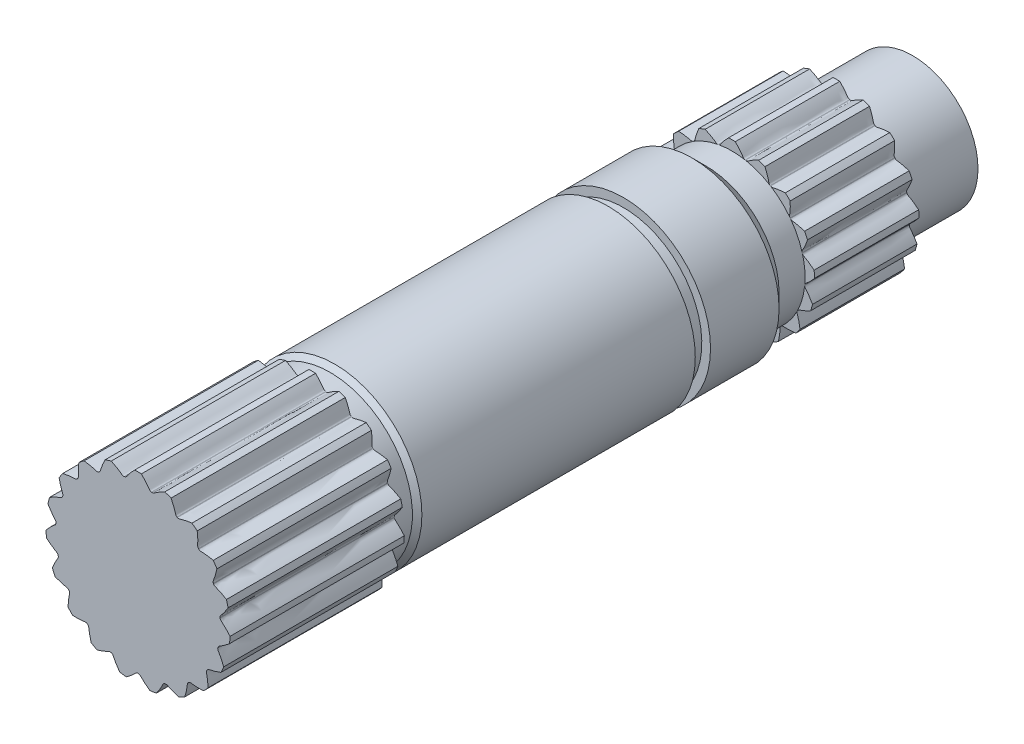
SolidWorks part; units mm, degrees
material "Alloy Steel"
ref_plane "Front Plane" through (0, 0, 0) normal (0, 0, 1) x (1, 0, 0)
ref_plane "Top Plane" through (0, 0, 0) normal (0, 1, 0) x (1, 0, 0)
ref_plane "Right Plane" through (0, 0, 0) normal (1, 0, 0) x (0, 0, -1)
sketch "Sketch12" plane through (0, 0, 0) normal (0, 0, 1) x (1, 0, 0)
  circle A0 centre (0, 0) radius 10
  dimension "D1" = 20
extrude "Shaft" add sketch "Sketch12" along normal mid plane 45
sketch "Sketch13" plane through (0, 0, 22.5) normal (0, 0, 1) x (1, 0, 0)
  circle A0 centre (0, 0) radius 9.4556
  dimension "D1" = 18.9113
extrude "Motor side relief" add sketch "Sketch13" along normal blind 1.587
sketch "Sketch14" plane through (0, 0, -22.5) normal (0, 0, -1) x (-1, 0, 0)
  circle A0 centre (0, 0) radius 8.3981
  dimension "D1" = 16.7963
extrude "Gear side relief" add sketch "Sketch14" along normal blind 1.587
sketch "Sketch15" plane through (0, 0, 24.087) normal (0, 0, 1) x (1, 0, 0)
  line L0 (5.7898, -7.4758) -> (5.8078, -7.4618)
  line L1 (5.8078, -7.4618) -> (5.8257, -7.4478)
  line L2 (7.9035, -5.1908) -> (7.9159, -5.1717)
  line L3 (7.9159, -5.1717) -> (7.9284, -5.1527)
  line L4 (9.1607, -2.3432) -> (9.1663, -2.3212)
  line L5 (9.1663, -2.3212) -> (9.1719, -2.2992)
  line L6 (9.4252, 0.7582) -> (9.4233, 0.7808)
  line L7 (9.4233, 0.7808) -> (9.4214, 0.8035)
  line L8 (8.6683, 3.7775) -> (8.6592, 3.7983)
  line L9 (8.6592, 3.7983) -> (8.6501, 3.8191)
  line L10 (6.9721, 6.3874) -> (6.9567, 6.4041)
  line L11 (6.9567, 6.4041) -> (6.9413, 6.4208)
  line L12 (4.5204, 8.3051) -> (4.5004, 8.316)
  line L13 (4.5004, 8.316) -> (4.4804, 8.3268)
  line L14 (1.5788, 9.3229) -> (1.5563, 9.3267)
  line L15 (1.5563, 9.3267) -> (1.5339, 9.3304)
  line L16 (-1.5339, 9.3304) -> (-1.5563, 9.3267)
  line L17 (-1.5563, 9.3267) -> (-1.5788, 9.3229)
  line L18 (-4.4804, 8.3268) -> (-4.5004, 8.316)
  line L19 (-4.5004, 8.316) -> (-4.5204, 8.3051)
  line L20 (-6.9413, 6.4208) -> (-6.9567, 6.4041)
  line L21 (-6.9567, 6.4041) -> (-6.9721, 6.3874)
  line L22 (-8.6501, 3.8191) -> (-8.6592, 3.7983)
  line L23 (-8.6592, 3.7983) -> (-8.6683, 3.7775)
  line L24 (-9.4214, 0.8035) -> (-9.4233, 0.7808)
  line L25 (-9.4233, 0.7808) -> (-9.4252, 0.7582)
  line L26 (-9.1719, -2.2992) -> (-9.1663, -2.3212)
  line L27 (-9.1663, -2.3212) -> (-9.1607, -2.3432)
  line L28 (-7.9284, -5.1527) -> (-7.9159, -5.1717)
  line L29 (-7.9159, -5.1717) -> (-7.9035, -5.1908)
  line L30 (-5.8257, -7.4478) -> (-5.8078, -7.4618)
  line L31 (-5.8078, -7.4618) -> (-5.7898, -7.4758)
  line L32 (-3.0917, -8.9359) -> (-3.0702, -8.9433)
  line L33 (-3.0702, -8.9433) -> (-3.0487, -8.9507)
  line L34 (-0.0227, -9.4556) -> (0, -9.4556)
  line L35 (0, -9.4556) -> (0.0227, -9.4556)
  line L36 (3.0487, -8.9507) -> (3.0702, -8.9433)
  line L37 (3.0702, -8.9433) -> (3.0917, -8.9359)
  arc A0 (4.6925, -9.4774) -> (5.3676, -9.1121) centre (0, 0) ccw
  arc A1 (7.5156, -7.4402) -> (8.0355, -6.8755) centre (0, 0) ccw
  arc A2 (9.5242, -4.5968) -> (9.8326, -3.8939) centre (0, 0) ccw
  arc A3 (10.5007, -1.2552) -> (10.5641, -0.4903) centre (0, 0) ccw
  arc A4 (10.3394, 2.2224) -> (10.1509, 2.9665) centre (0, 0) ccw
  arc A5 (9.0575, 5.4591) -> (8.6377, 6.1017) centre (0, 0) ccw
  arc A6 (6.7942, 8.1043) -> (6.1885, 8.5758) centre (0, 0) ccw
  arc A7 (3.7946, 9.8713) -> (3.0686, 10.1205) centre (0, 0) ccw
  arc A8 (0.3838, 10.5685) -> (-0.3838, 10.5685) centre (0, 0) ccw
  arc A9 (-3.0686, 10.1205) -> (-3.7946, 9.8713) centre (0, 0) ccw
  arc A10 (-6.1885, 8.5758) -> (-6.7942, 8.1043) centre (0, 0) ccw
  arc A11 (-8.6377, 6.1017) -> (-9.0575, 5.4591) centre (0, 0) ccw
  arc A12 (-10.1509, 2.9665) -> (-10.3394, 2.2224) centre (0, 0) ccw
  arc A13 (-10.5641, -0.4903) -> (-10.5007, -1.2552) centre (0, 0) ccw
  arc A14 (-9.8326, -3.8939) -> (-9.5242, -4.5968) centre (0, 0) ccw
  arc A15 (-8.0355, -6.8755) -> (-7.5156, -7.4402) centre (0, 0) ccw
  arc A16 (-5.3676, -9.1121) -> (-4.6925, -9.4774) centre (0, 0) ccw
  arc A17 (-2.1181, -10.3612) -> (-1.361, -10.4876) centre (0, 0) ccw
  arc A18 (1.361, -10.4876) -> (2.1181, -10.3612) centre (0, 0) ccw
  spline S0 degree 3 poles (3.0917, -8.9359) (3.1544, -8.9142) (3.2184, -8.911) (3.3396, -8.938) (3.397, -8.9729) (3.5767, -9.0624) (3.828, -9.1783) (4.24, -9.3384) (4.5379, -9.4334) (4.6925, -9.4774) knots 0 0 0 0 0.125 0.125 0.25 0.25 0.5 0.75 1 1 1 1
  spline S1 degree 3 poles (5.3676, -9.1121) (5.4153, -8.9586) (5.4987, -8.6572) (5.5901, -8.2247) (5.6305, -7.951) (5.6538, -7.7516) (5.656, -7.6845) (5.6997, -7.5682) (5.7374, -7.5164) (5.7898, -7.4758) knots 0 0 0 0 0.25 0.5 0.75 0.75 0.875 0.875 1 1 1 1
  spline S2 degree 3 poles (5.8257, -7.4478) (5.8779, -7.407) (5.9374, -7.3832) (6.0608, -7.3694) (6.1265, -7.3837) (6.3255, -7.41) (6.6008, -7.438) (7.0425, -7.4557) (7.3551, -7.4488) (7.5156, -7.4402) knots 0 0 0 0 0.125 0.125 0.25 0.25 0.5 0.75 1 1 1 1
  spline S3 degree 3 poles (8.0355, -6.8755) (8.0308, -6.7148) (8.0117, -6.4027) (7.9577, -5.964) (7.9071, -5.692) (7.8645, -5.4958) (7.8447, -5.4316) (7.8483, -5.3075) (7.8671, -5.2462) (7.9035, -5.1908) knots 0 0 0 0 0.25 0.5 0.75 0.75 0.875 0.875 1 1 1 1
  spline S4 degree 3 poles (7.9284, -5.1527) (7.9645, -5.0971) (8.013, -5.0552) (8.1253, -5.0021) (8.192, -4.9944) (8.3888, -4.9546) (8.6583, -4.8918) (9.0817, -4.765) (9.3752, -4.6571) (9.5242, -4.5968) knots 0 0 0 0 0.125 0.125 0.25 0.25 0.5 0.75 1 1 1 1
  spline S5 degree 3 poles (9.8326, -3.8939) (9.7759, -3.7434) (9.6566, -3.4544) (9.4631, -3.057) (9.3268, -2.8161) (9.2228, -2.6445) (9.1833, -2.5901) (9.1463, -2.4716) (9.1443, -2.4075) (9.1607, -2.3432) knots 0 0 0 0 0.25 0.5 0.75 0.75 0.875 0.875 1 1 1 1
  spline S6 degree 3 poles (9.1719, -2.2992) (9.188, -2.2349) (9.2203, -2.1795) (9.3092, -2.0928) (9.3699, -2.0638) (9.543, -1.9624) (9.7775, -1.8154) (10.1368, -1.558) (10.3793, -1.3606) (10.5007, -1.2552) knots 0 0 0 0 0.125 0.125 0.25 0.25 0.5 0.75 1 1 1 1
  spline S7 degree 3 poles (10.5641, -0.4903) (10.4617, -0.3663) (10.255, -0.1317) (9.9429, 0.1813) (9.7359, 0.3649) (9.5818, 0.4935) (9.5267, 0.532) (9.4533, 0.6322) (9.4305, 0.6921) (9.4252, 0.7582) knots 0 0 0 0 0.25 0.5 0.75 0.75 0.875 0.875 1 1 1 1
  spline S8 degree 3 poles (9.4214, 0.8035) (9.4158, 0.8695) (9.4284, 0.9324) (9.4844, 1.0433) (9.5323, 1.0904) (9.6631, 1.2426) (9.8372, 1.4577) (10.0935, 1.8179) (10.2588, 2.0833) (10.3394, 2.2224) knots 0 0 0 0 0.125 0.125 0.25 0.25 0.5 0.75 1 1 1 1
  spline S9 degree 3 poles (10.1509, 2.9665) (10.0138, 3.0504) (9.7422, 3.2052) (9.3453, 3.4) (9.0899, 3.5063) (8.9024, 3.5779) (8.8378, 3.5965) (8.7358, 3.6674) (8.6948, 3.7167) (8.6683, 3.7775) knots 0 0 0 0 0.25 0.5 0.75 0.75 0.875 0.875 1 1 1 1
  spline S10 degree 3 poles (8.6501, 3.8191) (8.6233, 3.8797) (8.6148, 3.9433) (8.6317, 4.0663) (8.6618, 4.1264) (8.7361, 4.3129) (8.8308, 4.5729) (8.9563, 4.9967) (9.0265, 5.3014) (9.0575, 5.4591) knots 0 0 0 0 0.125 0.125 0.25 0.25 0.5 0.75 1 1 1 1
  spline S11 degree 3 poles (8.6377, 6.1017) (8.4808, 6.1366) (8.1736, 6.1948) (7.735, 6.2502) (7.4588, 6.2678) (7.2583, 6.2747) (7.1911, 6.2713) (7.0717, 6.3052) (7.0169, 6.3385) (6.9721, 6.3874) knots 0 0 0 0 0.25 0.5 0.75 0.75 0.875 0.875 1 1 1 1
  spline S12 degree 3 poles (6.9413, 6.4208) (6.8963, 6.4695) (6.8676, 6.5268) (6.8437, 6.6487) (6.8526, 6.7153) (6.8624, 6.9158) (6.8676, 7.1925) (6.8486, 7.6341) (6.816, 7.9451) (6.7942, 8.1043) knots 0 0 0 0 0.125 0.125 0.25 0.25 0.5 0.75 1 1 1 1
  spline S13 degree 3 poles (6.1885, 8.5758) (6.0287, 8.5578) (5.7193, 8.5131) (5.2865, 8.4231) (5.0196, 8.3501) (4.8276, 8.2914) (4.7652, 8.2664) (4.6412, 8.2597) (4.5786, 8.2734) (4.5204, 8.3051) knots 0 0 0 0 0.25 0.5 0.75 0.75 0.875 0.875 1 1 1 1
  spline S14 degree 3 poles (4.4804, 8.3268) (4.422, 8.3582) (4.3763, 8.4031) (4.3141, 8.5106) (4.3009, 8.5765) (4.245, 8.7693) (4.1601, 9.0326) (3.9988, 9.4442) (3.8669, 9.7277) (3.7946, 9.8713) knots 0 0 0 0 0.125 0.125 0.25 0.25 0.5 0.75 1 1 1 1
  spline S15 degree 3 poles (3.0686, 10.1205) (2.9233, 10.0517) (2.6452, 9.9089) (2.2651, 9.6832) (2.0363, 9.5275) (1.8738, 9.4097) (1.8229, 9.3658) (1.7078, 9.3192) (1.6441, 9.3118) (1.5788, 9.3229) knots 0 0 0 0 0.25 0.5 0.75 0.75 0.875 0.875 1 1 1 1
  spline S16 degree 3 poles (1.5339, 9.3304) (1.4685, 9.3411) (1.4107, 9.3688) (1.3169, 9.4502) (1.283, 9.5083) (1.1676, 9.6725) (1.0018, 9.894) (0.7156, 10.2309) (0.4988, 10.4563) (0.3838, 10.5685) knots 0 0 0 0 0.125 0.125 0.25 0.25 0.5 0.75 1 1 1 1
  spline S17 degree 3 poles (-0.3838, 10.5685) (-0.4988, 10.4563) (-0.7156, 10.2309) (-1.0018, 9.894) (-1.1676, 9.6725) (-1.283, 9.5083) (-1.3169, 9.4502) (-1.4107, 9.3688) (-1.4685, 9.3411) (-1.5339, 9.3304) knots 0 0 0 0 0.25 0.5 0.75 0.75 0.875 0.875 1 1 1 1
  spline S18 degree 3 poles (-1.5788, 9.3229) (-1.6441, 9.3118) (-1.7078, 9.3192) (-1.8229, 9.3658) (-1.8738, 9.4097) (-2.0363, 9.5275) (-2.2651, 9.6832) (-2.6452, 9.9089) (-2.9233, 10.0517) (-3.0686, 10.1205) knots 0 0 0 0 0.125 0.125 0.25 0.25 0.5 0.75 1 1 1 1
  spline S19 degree 3 poles (-3.7946, 9.8713) (-3.8669, 9.7277) (-3.9988, 9.4442) (-4.1601, 9.0326) (-4.245, 8.7693) (-4.3009, 8.5765) (-4.3141, 8.5106) (-4.3763, 8.4031) (-4.422, 8.3582) (-4.4804, 8.3268) knots 0 0 0 0 0.25 0.5 0.75 0.75 0.875 0.875 1 1 1 1
  spline S20 degree 3 poles (-4.5204, 8.3051) (-4.5786, 8.2734) (-4.6412, 8.2597) (-4.7652, 8.2664) (-4.8276, 8.2914) (-5.0196, 8.3501) (-5.2865, 8.4231) (-5.7193, 8.5131) (-6.0287, 8.5578) (-6.1885, 8.5758) knots 0 0 0 0 0.125 0.125 0.25 0.25 0.5 0.75 1 1 1 1
  spline S21 degree 3 poles (-6.7942, 8.1043) (-6.816, 7.9451) (-6.8486, 7.6341) (-6.8676, 7.1925) (-6.8624, 6.9158) (-6.8526, 6.7153) (-6.8437, 6.6487) (-6.8676, 6.5268) (-6.8963, 6.4695) (-6.9413, 6.4208) knots 0 0 0 0 0.25 0.5 0.75 0.75 0.875 0.875 1 1 1 1
  spline S22 degree 3 poles (-6.9721, 6.3874) (-7.0169, 6.3385) (-7.0717, 6.3052) (-7.1911, 6.2713) (-7.2583, 6.2747) (-7.4588, 6.2678) (-7.735, 6.2502) (-8.1736, 6.1948) (-8.4808, 6.1366) (-8.6377, 6.1017) knots 0 0 0 0 0.125 0.125 0.25 0.25 0.5 0.75 1 1 1 1
  spline S23 degree 3 poles (-9.0575, 5.4591) (-9.0265, 5.3014) (-8.9563, 4.9967) (-8.8308, 4.5729) (-8.7361, 4.3129) (-8.6618, 4.1264) (-8.6317, 4.0663) (-8.6148, 3.9433) (-8.6233, 3.8797) (-8.6501, 3.8191) knots 0 0 0 0 0.25 0.5 0.75 0.75 0.875 0.875 1 1 1 1
  spline S24 degree 3 poles (-8.6683, 3.7775) (-8.6948, 3.7167) (-8.7358, 3.6674) (-8.8378, 3.5965) (-8.9024, 3.5779) (-9.0899, 3.5063) (-9.3453, 3.4) (-9.7422, 3.2052) (-10.0138, 3.0504) (-10.1509, 2.9665) knots 0 0 0 0 0.125 0.125 0.25 0.25 0.5 0.75 1 1 1 1
  spline S25 degree 3 poles (-10.3394, 2.2224) (-10.2588, 2.0833) (-10.0935, 1.8179) (-9.8372, 1.4577) (-9.6631, 1.2426) (-9.5323, 1.0904) (-9.4844, 1.0433) (-9.4284, 0.9324) (-9.4158, 0.8695) (-9.4214, 0.8035) knots 0 0 0 0 0.25 0.5 0.75 0.75 0.875 0.875 1 1 1 1
  spline S26 degree 3 poles (-9.4252, 0.7582) (-9.4305, 0.6921) (-9.4533, 0.6322) (-9.5267, 0.532) (-9.5818, 0.4935) (-9.7359, 0.3649) (-9.9429, 0.1813) (-10.255, -0.1317) (-10.4617, -0.3663) (-10.5641, -0.4903) knots 0 0 0 0 0.125 0.125 0.25 0.25 0.5 0.75 1 1 1 1
  spline S27 degree 3 poles (-10.5007, -1.2552) (-10.3793, -1.3606) (-10.1368, -1.558) (-9.7775, -1.8154) (-9.543, -1.9624) (-9.3699, -2.0638) (-9.3092, -2.0928) (-9.2203, -2.1795) (-9.188, -2.2349) (-9.1719, -2.2992) knots 0 0 0 0 0.25 0.5 0.75 0.75 0.875 0.875 1 1 1 1
  spline S28 degree 3 poles (-9.1607, -2.3432) (-9.1443, -2.4075) (-9.1463, -2.4716) (-9.1833, -2.5901) (-9.2228, -2.6445) (-9.3268, -2.8161) (-9.4631, -3.057) (-9.6566, -3.4544) (-9.7759, -3.7434) (-9.8326, -3.8939) knots 0 0 0 0 0.125 0.125 0.25 0.25 0.5 0.75 1 1 1 1
  spline S29 degree 3 poles (-9.5242, -4.5968) (-9.3752, -4.6571) (-9.0817, -4.765) (-8.6583, -4.8918) (-8.3888, -4.9546) (-8.192, -4.9944) (-8.1253, -5.0021) (-8.013, -5.0552) (-7.9645, -5.0971) (-7.9284, -5.1527) knots 0 0 0 0 0.25 0.5 0.75 0.75 0.875 0.875 1 1 1 1
  spline S30 degree 3 poles (-7.9035, -5.1908) (-7.8671, -5.2462) (-7.8483, -5.3075) (-7.8447, -5.4316) (-7.8645, -5.4958) (-7.9071, -5.692) (-7.9577, -5.964) (-8.0117, -6.4027) (-8.0308, -6.7148) (-8.0355, -6.8755) knots 0 0 0 0 0.125 0.125 0.25 0.25 0.5 0.75 1 1 1 1
  spline S31 degree 3 poles (-7.5156, -7.4402) (-7.3551, -7.4488) (-7.0425, -7.4557) (-6.6008, -7.438) (-6.3255, -7.41) (-6.1265, -7.3837) (-6.0608, -7.3694) (-5.9374, -7.3832) (-5.8779, -7.407) (-5.8257, -7.4478) knots 0 0 0 0 0.25 0.5 0.75 0.75 0.875 0.875 1 1 1 1
  spline S32 degree 3 poles (-5.7898, -7.4758) (-5.7374, -7.5164) (-5.6997, -7.5682) (-5.656, -7.6845) (-5.6538, -7.7516) (-5.6305, -7.951) (-5.5901, -8.2247) (-5.4987, -8.6572) (-5.4153, -8.9586) (-5.3676, -9.1121) knots 0 0 0 0 0.125 0.125 0.25 0.25 0.5 0.75 1 1 1 1
  spline S33 degree 3 poles (-4.6925, -9.4774) (-4.5379, -9.4334) (-4.24, -9.3384) (-3.828, -9.1783) (-3.5767, -9.0624) (-3.397, -8.9729) (-3.3396, -8.938) (-3.2184, -8.911) (-3.1544, -8.9142) (-3.0917, -8.9359) knots 0 0 0 0 0.25 0.5 0.75 0.75 0.875 0.875 1 1 1 1
  spline S34 degree 3 poles (-3.0487, -8.9507) (-2.986, -8.972) (-2.9335, -9.0088) (-2.8544, -9.1046) (-2.8306, -9.1674) (-2.7437, -9.3484) (-2.6166, -9.5942) (-2.3898, -9.9736) (-2.2131, -10.2315) (-2.1181, -10.3612) knots 0 0 0 0 0.125 0.125 0.25 0.25 0.5 0.75 1 1 1 1
  spline S35 degree 3 poles (-1.361, -10.4876) (-1.229, -10.3957) (-0.9781, -10.2091) (-0.6404, -9.9239) (-0.4404, -9.7327) (-0.2995, -9.5898) (-0.2565, -9.5381) (-0.1506, -9.4732) (-0.089, -9.4555) (-0.0227, -9.4556) knots 0 0 0 0 0.25 0.5 0.75 0.75 0.875 0.875 1 1 1 1
  spline S36 degree 3 poles (0.0227, -9.4556) (0.089, -9.4555) (0.1506, -9.4732) (0.2565, -9.5381) (0.2995, -9.5898) (0.4404, -9.7327) (0.6404, -9.9239) (0.9781, -10.2091) (1.229, -10.3957) (1.361, -10.4876) knots 0 0 0 0 0.125 0.125 0.25 0.25 0.5 0.75 1 1 1 1
  spline S37 degree 3 poles (2.1181, -10.3612) (2.2131, -10.2315) (2.3898, -9.9736) (2.6166, -9.5942) (2.7437, -9.3484) (2.8306, -9.1674) (2.8544, -9.1046) (2.9335, -9.0088) (2.986, -8.972) (3.0487, -8.9507) knots 0 0 0 0 0.25 0.5 0.75 0.75 0.875 0.875 1 1 1 1
extrude "Boss-Extrude8" add sketch "Sketch15" along normal blind 20
sketch "Sketch17" plane through (0, 0, -24.087) normal (0, 0, -1) x (-1, 0, 0)
  line L38 (4.4402, 7.1283) -> (4.4211, 7.1402)
  line L39 (4.4211, 7.1402) -> (4.4019, 7.1521)
  line L40 (1.5653, 8.251) -> (1.5432, 8.2552)
  line L41 (1.5432, 8.2552) -> (1.521, 8.2593)
  line L42 (-1.521, 8.2593) -> (-1.5432, 8.2552)
  line L43 (-1.5432, 8.2552) -> (-1.5653, 8.251)
  line L44 (-4.4019, 7.1521) -> (-4.4211, 7.1402)
  line L45 (-4.4211, 7.1402) -> (-4.4402, 7.1283)
  line L46 (-6.6882, 5.079) -> (-6.7019, 5.061)
  line L47 (-6.7019, 5.061) -> (-6.7154, 5.043)
  line L48 (-8.0713, 2.32) -> (-8.0776, 2.2983)
  line L49 (-8.0776, 2.2983) -> (-8.0837, 2.2766)
  line L50 (-8.3644, -0.7524) -> (-8.3623, -0.7749)
  line L51 (-8.3623, -0.7749) -> (-8.3602, -0.7973)
  line L52 (-7.5277, -3.7232) -> (-7.5177, -3.7434)
  line L53 (-7.5177, -3.7434) -> (-7.5076, -3.7636)
  line L54 (-5.6744, -6.1911) -> (-5.6578, -6.2063)
  line L55 (-5.6578, -6.2063) -> (-5.6411, -6.2215)
  line L56 (-3.0548, -7.8229) -> (-3.0338, -7.831)
  line L57 (-3.0338, -7.831) -> (-3.0127, -7.8392)
  line L58 (-0.0226, -8.3981) -> (0, -8.3981)
  line L59 (0, -8.3981) -> (0.0226, -8.3981)
  line L60 (3.0127, -7.8392) -> (3.0338, -7.831)
  line L61 (3.0338, -7.831) -> (3.0548, -7.8229)
  line L62 (5.6411, -6.2215) -> (5.6578, -6.2063)
  line L63 (5.6578, -6.2063) -> (5.6744, -6.1911)
  line L64 (7.5076, -3.7636) -> (7.5177, -3.7434)
  line L65 (7.5177, -3.7434) -> (7.5277, -3.7232)
  line L66 (8.3602, -0.7973) -> (8.3623, -0.7749)
  line L67 (8.3623, -0.7749) -> (8.3644, -0.7524)
  line L68 (8.0837, 2.2766) -> (8.0776, 2.2983)
  line L69 (8.0776, 2.2983) -> (8.0713, 2.32)
  line L70 (6.7154, 5.043) -> (6.7019, 5.061)
  line L71 (6.7019, 5.061) -> (6.6882, 5.079)
  arc A19 (6.6912, 6.7683) -> (6.1221, 7.2872) centre (0, 0) ccw
  arc A20 (3.7944, 8.7284) -> (3.0762, 9.0066) centre (0, 0) ccw
  arc A21 (0.3851, 9.5097) -> (-0.3851, 9.5097) centre (0, 0) ccw
  arc A22 (-3.0762, 9.0066) -> (-3.7944, 8.7284) centre (0, 0) ccw
  arc A23 (-6.1221, 7.2872) -> (-6.6912, 6.7683) centre (0, 0) ccw
  arc A24 (-8.3411, 4.5835) -> (-8.6844, 3.8941) centre (0, 0) ccw
  arc A25 (-9.4336, 1.2609) -> (-9.5047, 0.494) centre (0, 0) ccw
  arc A26 (-9.2521, -2.2321) -> (-9.0413, -2.9728) centre (0, 0) ccw
  arc A27 (-7.821, -5.4236) -> (-7.3569, -6.0382) centre (0, 0) ccw
  arc A28 (-5.3336, -7.8826) -> (-4.6788, -8.288) centre (0, 0) ccw
  arc A29 (-2.1259, -9.277) -> (-1.3689, -9.4185) centre (0, 0) ccw
  arc A30 (1.3689, -9.4185) -> (2.1259, -9.277) centre (0, 0) ccw
  arc A31 (4.6788, -8.288) -> (5.3336, -7.8826) centre (0, 0) ccw
  arc A32 (7.3569, -6.0382) -> (7.821, -5.4236) centre (0, 0) ccw
  arc A33 (9.0413, -2.9728) -> (9.2521, -2.2321) centre (0, 0) ccw
  arc A34 (9.5047, 0.494) -> (9.4336, 1.2609) centre (0, 0) ccw
  arc A35 (8.6844, 3.8941) -> (8.3411, 4.5835) centre (0, 0) ccw
  spline S0 degree 3 poles (6.6882, 5.079) (6.6486, 5.1312) (6.6257, 5.1903) (6.6128, 5.3124) (6.6277, 5.3769) (6.657, 5.5736) (6.6884, 5.8472) (6.7084, 6.2901) (6.7009, 6.6058) (6.6912, 6.7683) knots 0 0 0 0 0.125 0.125 0.25 0.25 0.5 0.75 1 1 1 1 weights 1 1 1 1 1 1 1 1 1 1
  spline S1 degree 3 poles (6.1221, 7.2872) (5.9593, 7.2818) (5.6443, 7.2602) (5.2052, 7.1994) (4.9356, 7.1428) (4.7425, 7.0956) (4.6796, 7.0748) (4.5569, 7.0763) (4.4958, 7.0937) (4.4402, 7.1283) knots 0 0 0 0 0.25 0.5 0.75 0.75 0.875 0.875 1 1 1 1 weights 1 1 1 1 1 1 1 1 1 1
  spline S2 degree 3 poles (4.4019, 7.1521) (4.3461, 7.1864) (4.3033, 7.2333) (4.2472, 7.3425) (4.2378, 7.4081) (4.194, 7.602) (4.1245, 7.8685) (3.9832, 8.2887) (3.8621, 8.5804) (3.7944, 8.7284) knots 0 0 0 0 0.125 0.125 0.25 0.25 0.5 0.75 1 1 1 1 weights 1 1 1 1 1 1 1 1 1 1
  spline S3 degree 3 poles (3.0762, 9.0066) (2.9264, 8.9428) (2.6405, 8.8089) (2.253, 8.5935) (2.022, 8.4434) (1.859, 8.3296) (1.8079, 8.2875) (1.6929, 8.2446) (1.6297, 8.2388) (1.5653, 8.251) knots 0 0 0 0 0.25 0.5 0.75 0.75 0.875 0.875 1 1 1 1 weights 1 1 1 1 1 1 1 1 1 1
  spline S4 degree 3 poles (1.521, 8.2593) (1.4566, 8.2711) (1.3997, 8.2994) (1.308, 8.3809) (1.2755, 8.4387) (1.1646, 8.6037) (1.0035, 8.8271) (0.7199, 9.1679) (0.5017, 9.3961) (0.3851, 9.5097) knots 0 0 0 0 0.125 0.125 0.25 0.25 0.5 0.75 1 1 1 1 weights 1 1 1 1 1 1 1 1 1 1
  spline S5 degree 3 poles (-0.3851, 9.5097) (-0.5017, 9.3961) (-0.7199, 9.1679) (-1.0035, 8.8271) (-1.1646, 8.6037) (-1.2755, 8.4387) (-1.308, 8.3809) (-1.3997, 8.2994) (-1.4566, 8.2711) (-1.521, 8.2593) knots 0 0 0 0 0.25 0.5 0.75 0.75 0.875 0.875 1 1 1 1 weights 1 1 1 1 1 1 1 1 1 1
  spline S6 degree 3 poles (-1.5653, 8.251) (-1.6297, 8.2388) (-1.6929, 8.2446) (-1.8079, 8.2875) (-1.859, 8.3296) (-2.022, 8.4434) (-2.253, 8.5935) (-2.6405, 8.8089) (-2.9264, 8.9428) (-3.0762, 9.0066) knots 0 0 0 0 0.125 0.125 0.25 0.25 0.5 0.75 1 1 1 1 weights 1 1 1 1 1 1 1 1 1 1
  spline S7 degree 3 poles (-3.7944, 8.7284) (-3.8621, 8.5804) (-3.9832, 8.2887) (-4.1245, 7.8685) (-4.194, 7.602) (-4.2378, 7.4081) (-4.2472, 7.3425) (-4.3033, 7.2333) (-4.3461, 7.1864) (-4.4019, 7.1521) knots 0 0 0 0 0.25 0.5 0.75 0.75 0.875 0.875 1 1 1 1 weights 1 1 1 1 1 1 1 1 1 1
  spline S8 degree 3 poles (-4.4402, 7.1283) (-4.4958, 7.0937) (-4.5569, 7.0763) (-4.6796, 7.0748) (-4.7425, 7.0956) (-4.9356, 7.1428) (-5.2052, 7.1994) (-5.6443, 7.2602) (-5.9593, 7.2818) (-6.1221, 7.2872) knots 0 0 0 0 0.125 0.125 0.25 0.25 0.5 0.75 1 1 1 1 weights 1 1 1 1 1 1 1 1 1 1
  spline S9 degree 3 poles (-6.6912, 6.7683) (-6.7009, 6.6058) (-6.7084, 6.2901) (-6.6884, 5.8472) (-6.657, 5.5736) (-6.6277, 5.3769) (-6.6128, 5.3124) (-6.6257, 5.1903) (-6.6486, 5.1312) (-6.6882, 5.079) knots 0 0 0 0 0.25 0.5 0.75 0.75 0.875 0.875 1 1 1 1 weights 1 1 1 1 1 1 1 1 1 1
  spline S10 degree 3 poles (-6.7154, 5.043) (-6.7548, 4.9906) (-6.8054, 4.9523) (-6.9193, 4.9066) (-6.9854, 4.9033) (-7.1826, 4.8775) (-7.4544, 4.8329) (-7.8859, 4.7309) (-8.1874, 4.6373) (-8.3411, 4.5835) knots 0 0 0 0 0.125 0.125 0.25 0.25 0.5 0.75 1 1 1 1 weights 1 1 1 1 1 1 1 1 1 1
  spline S11 degree 3 poles (-8.6844, 3.8941) (-8.6347, 3.7391) (-8.5277, 3.442) (-8.349, 3.0363) (-8.2209, 2.7925) (-8.1225, 2.6196) (-8.0853, 2.5648) (-8.0532, 2.4464) (-8.0533, 2.3829) (-8.0713, 2.32) knots 0 0 0 0 0.25 0.5 0.75 0.75 0.875 0.875 1 1 1 1 weights 1 1 1 1 1 1 1 1 1 1
  spline S12 degree 3 poles (-8.0837, 2.2766) (-8.1015, 2.2135) (-8.1348, 2.1595) (-8.2245, 2.0757) (-8.285, 2.0487) (-8.4596, 1.9535) (-8.6968, 1.8137) (-9.0624, 1.5628) (-9.3097, 1.3665) (-9.4336, 1.2609) knots 0 0 0 0 0.125 0.125 0.25 0.25 0.5 0.75 1 1 1 1 weights 1 1 1 1 1 1 1 1 1 1
  spline S13 degree 3 poles (-9.5047, 0.494) (-9.4023, 0.3674) (-9.1952, 0.129) (-8.882, -0.1848) (-8.6745, -0.3658) (-8.5204, -0.4915) (-8.4659, -0.5291) (-8.3931, -0.628) (-8.3702, -0.6872) (-8.3644, -0.7524) knots 0 0 0 0 0.25 0.5 0.75 0.75 0.875 0.875 1 1 1 1 weights 1 1 1 1 1 1 1 1 1 1
  spline S14 degree 3 poles (-8.3602, -0.7973) (-8.354, -0.8625) (-8.3656, -0.925) (-8.419, -1.0355) (-8.4656, -1.0825) (-8.594, -1.2344) (-8.7647, -1.4504) (-9.0149, -1.8164) (-9.1747, -2.0888) (-9.2521, -2.2321) knots 0 0 0 0 0.125 0.125 0.25 0.25 0.5 0.75 1 1 1 1 weights 1 1 1 1 1 1 1 1 1 1
  spline S15 degree 3 poles (-9.0413, -2.9728) (-8.9001, -3.0539) (-8.6209, -3.2014) (-8.2155, -3.3809) (-7.9566, -3.4747) (-7.7675, -3.5362) (-7.7031, -3.5516) (-7.5995, -3.6175) (-7.5568, -3.6645) (-7.5277, -3.7232) knots 0 0 0 0 0.25 0.5 0.75 0.75 0.875 0.875 1 1 1 1 weights 1 1 1 1 1 1 1 1 1 1
  spline S16 degree 3 poles (-7.5076, -3.7636) (-7.4783, -3.8221) (-7.4666, -3.8845) (-7.4764, -4.0068) (-7.5029, -4.0675) (-7.5678, -4.2555) (-7.6489, -4.5187) (-7.75, -4.9504) (-7.8006, -5.262) (-7.821, -5.4236) knots 0 0 0 0 0.125 0.125 0.25 0.25 0.5 0.75 1 1 1 1 weights 1 1 1 1 1 1 1 1 1 1
  spline S17 degree 3 poles (-7.3569, -6.0382) (-7.1959, -6.0628) (-6.8823, -6.0994) (-6.4394, -6.1203) (-6.1641, -6.1143) (-5.9655, -6.1033) (-5.8999, -6.0945) (-5.7795, -6.1185) (-5.7227, -6.1468) (-5.6744, -6.1911) knots 0 0 0 0 0.25 0.5 0.75 0.75 0.875 0.875 1 1 1 1 weights 1 1 1 1 1 1 1 1 1 1
  spline S18 degree 3 poles (-5.6411, -6.2215) (-5.5926, -6.2655) (-5.5591, -6.3194) (-5.5241, -6.437) (-5.5269, -6.5032) (-5.5195, -6.7019) (-5.5001, -6.9766) (-5.4384, -7.4157) (-5.373, -7.7246) (-5.3336, -7.8826) knots 0 0 0 0 0.125 0.125 0.25 0.25 0.5 0.75 1 1 1 1 weights 1 1 1 1 1 1 1 1 1 1
  spline S19 degree 3 poles (-4.6788, -8.288) (-4.5198, -8.2528) (-4.2142, -8.1737) (-3.7936, -8.0332) (-3.5391, -7.9281) (-3.3579, -7.8462) (-3.2999, -7.8142) (-3.179, -7.7931) (-3.1158, -7.799) (-3.0548, -7.8229) knots 0 0 0 0 0.25 0.5 0.75 0.75 0.875 0.875 1 1 1 1 weights 1 1 1 1 1 1 1 1 1 1
  spline S20 degree 3 poles (-3.0127, -7.8392) (-2.9516, -7.8627) (-2.9009, -7.9009) (-2.8257, -7.9979) (-2.8044, -8.0606) (-2.7257, -8.2432) (-2.6084, -8.4924) (-2.3923, -8.8795) (-2.2197, -9.1439) (-2.1259, -9.277) knots 0 0 0 0 0.125 0.125 0.25 0.25 0.5 0.75 1 1 1 1 weights 1 1 1 1 1 1 1 1 1 1
  spline S21 degree 3 poles (-1.3689, -9.4185) (-1.2333, -9.3283) (-0.9769, -9.1441) (-0.6355, -8.8612) (-0.4361, -8.6712) (-0.2968, -8.5294) (-0.2543, -8.4786) (-0.1491, -8.4153) (-0.0881, -8.3979) (-0.0226, -8.3981) knots 0 0 0 0 0.25 0.5 0.75 0.75 0.875 0.875 1 1 1 1 weights 1 1 1 1 1 1 1 1 1 1
  spline S22 degree 3 poles (0.0226, -8.3981) (0.0881, -8.3979) (0.1491, -8.4153) (0.2543, -8.4786) (0.2968, -8.5294) (0.4361, -8.6712) (0.6355, -8.8612) (0.9769, -9.1441) (1.2333, -9.3283) (1.3689, -9.4185) knots 0 0 0 0 0.125 0.125 0.25 0.25 0.5 0.75 1 1 1 1 weights 1 1 1 1 1 1 1 1 1 1
  spline S23 degree 3 poles (2.1259, -9.277) (2.2197, -9.1439) (2.3923, -8.8795) (2.6084, -8.4924) (2.7257, -8.2432) (2.8044, -8.0606) (2.8257, -7.9979) (2.9009, -7.9009) (2.9516, -7.8627) (3.0127, -7.8392) knots 0 0 0 0 0.25 0.5 0.75 0.75 0.875 0.875 1 1 1 1 weights 1 1 1 1 1 1 1 1 1 1
  spline S24 degree 3 poles (3.0548, -7.8229) (3.1158, -7.799) (3.179, -7.7931) (3.2999, -7.8142) (3.3579, -7.8462) (3.5391, -7.9281) (3.7936, -8.0332) (4.2142, -8.1737) (4.5198, -8.2528) (4.6788, -8.288) knots 0 0 0 0 0.125 0.125 0.25 0.25 0.5 0.75 1 1 1 1 weights 1 1 1 1 1 1 1 1 1 1
  spline S25 degree 3 poles (5.3336, -7.8826) (5.373, -7.7246) (5.4384, -7.4157) (5.5001, -6.9766) (5.5195, -6.7019) (5.5269, -6.5032) (5.5241, -6.437) (5.5591, -6.3194) (5.5926, -6.2655) (5.6411, -6.2215) knots 0 0 0 0 0.25 0.5 0.75 0.75 0.875 0.875 1 1 1 1 weights 1 1 1 1 1 1 1 1 1 1
  spline S26 degree 3 poles (5.6744, -6.1911) (5.7227, -6.1468) (5.7795, -6.1185) (5.8999, -6.0945) (5.9655, -6.1033) (6.1641, -6.1143) (6.4394, -6.1203) (6.8823, -6.0994) (7.1959, -6.0628) (7.3569, -6.0382) knots 0 0 0 0 0.125 0.125 0.25 0.25 0.5 0.75 1 1 1 1 weights 1 1 1 1 1 1 1 1 1 1
  spline S27 degree 3 poles (7.821, -5.4236) (7.8006, -5.262) (7.75, -4.9504) (7.6489, -4.5187) (7.5678, -4.2555) (7.5029, -4.0675) (7.4764, -4.0068) (7.4666, -3.8845) (7.4783, -3.8221) (7.5076, -3.7636) knots 0 0 0 0 0.25 0.5 0.75 0.75 0.875 0.875 1 1 1 1 weights 1 1 1 1 1 1 1 1 1 1
  spline S28 degree 3 poles (7.5277, -3.7232) (7.5568, -3.6645) (7.5995, -3.6175) (7.7031, -3.5516) (7.7675, -3.5362) (7.9566, -3.4747) (8.2155, -3.3809) (8.6209, -3.2014) (8.9001, -3.0539) (9.0413, -2.9728) knots 0 0 0 0 0.125 0.125 0.25 0.25 0.5 0.75 1 1 1 1 weights 1 1 1 1 1 1 1 1 1 1
  spline S29 degree 3 poles (9.2521, -2.2321) (9.1747, -2.0888) (9.0149, -1.8164) (8.7647, -1.4504) (8.594, -1.2344) (8.4656, -1.0825) (8.419, -1.0355) (8.3656, -0.925) (8.354, -0.8625) (8.3602, -0.7973) knots 0 0 0 0 0.25 0.5 0.75 0.75 0.875 0.875 1 1 1 1 weights 1 1 1 1 1 1 1 1 1 1
  spline S30 degree 3 poles (8.3644, -0.7524) (8.3702, -0.6872) (8.3931, -0.628) (8.4659, -0.5291) (8.5204, -0.4915) (8.6745, -0.3658) (8.882, -0.1848) (9.1952, 0.129) (9.4023, 0.3674) (9.5047, 0.494) knots 0 0 0 0 0.125 0.125 0.25 0.25 0.5 0.75 1 1 1 1 weights 1 1 1 1 1 1 1 1 1 1
  spline S31 degree 3 poles (9.4336, 1.2609) (9.3097, 1.3665) (9.0624, 1.5628) (8.6968, 1.8137) (8.4596, 1.9535) (8.285, 2.0487) (8.2245, 2.0757) (8.1348, 2.1595) (8.1015, 2.2135) (8.0837, 2.2766) knots 0 0 0 0 0.25 0.5 0.75 0.75 0.875 0.875 1 1 1 1 weights 1 1 1 1 1 1 1 1 1 1
  spline S32 degree 3 poles (8.0713, 2.32) (8.0533, 2.3829) (8.0532, 2.4464) (8.0853, 2.5648) (8.1225, 2.6196) (8.2209, 2.7925) (8.349, 3.0363) (8.5277, 3.442) (8.6347, 3.7391) (8.6844, 3.8941) knots 0 0 0 0 0.125 0.125 0.25 0.25 0.5 0.75 1 1 1 1 weights 1 1 1 1 1 1 1 1 1 1
  spline S33 degree 3 poles (8.3411, 4.5835) (8.1874, 4.6373) (7.8858, 4.731) (7.4544, 4.8329) (7.1826, 4.8775) (6.9854, 4.9033) (6.9193, 4.9066) (6.8054, 4.9523) (6.7548, 4.9906) (6.7154, 5.043) knots 0 0 0 0 0.25 0.5 0.75 0.75 0.875 0.875 1 1 1 1 weights 1 1 1 1 1 1 1 1 1 1
extrude "Sun Gear Spline" add sketch "Sketch17" along normal blind 12
sketch "Sketch20" plane through (0, 0, -36.087) normal (0, 0, -1) x (-1, 0, 0)
  circle A0 centre (0, 0) radius 8.3981
chamfer "Chamfer1" distance 3 angle 45 1 edges at (10, 0, -22.5)
chamfer "Chamfer3" distance 1 angle 45 1 edges at (10, 0, 22.5)
sketch "Sketch21" plane through (0, 0, 0) normal (1, 0, 0) x (0, 0, -1)
  line L0 (0, 0) -> (72.5071, 0) construction
  line L9 (36.087, 0) -> (36.087, 7.5)
  line L10 (36.087, 7.1521) -> (36.087, 8.7284) construction
  line L11 (36.087, 7.5) -> (44.837, 7.5)
  line L12 (36.087, 0) -> (44.837, 0)
  line L13 (44.837, 7.5) -> (44.837, 0)
  dimension "D1" = 15
  dimension "D2" = 8.75
revolve "Revolve1" add sketch "Sketch21" angle 360 about L0
sketch "Sketch23" plane through (0, 0, -30.087) normal (-0.5347, 0.845, 0) x (-0.845, -0.5347, 0)
  line L0 (10, 20.2042) -> (9, 20.2042)
  line L1 (9, 20.2042) -> (9, 18.4542)
  line L2 (9, 18.4542) -> (10, 18.4542)
  line L3 (10, 18.4542) -> (10, 20.2042)
  line L4 (10, 10.587) -> (10, 51.587) construction
  line L5 (-13.85, 20.2042) -> (13.85, 20.2042) construction
  line L7 (0, 185.3358) -> (0, -121.609) construction
  dimension "D1" = 1.75
  dimension "D2" = 1
revolve "snap ring" cut sketch "Sketch23" angle 360 about L7
